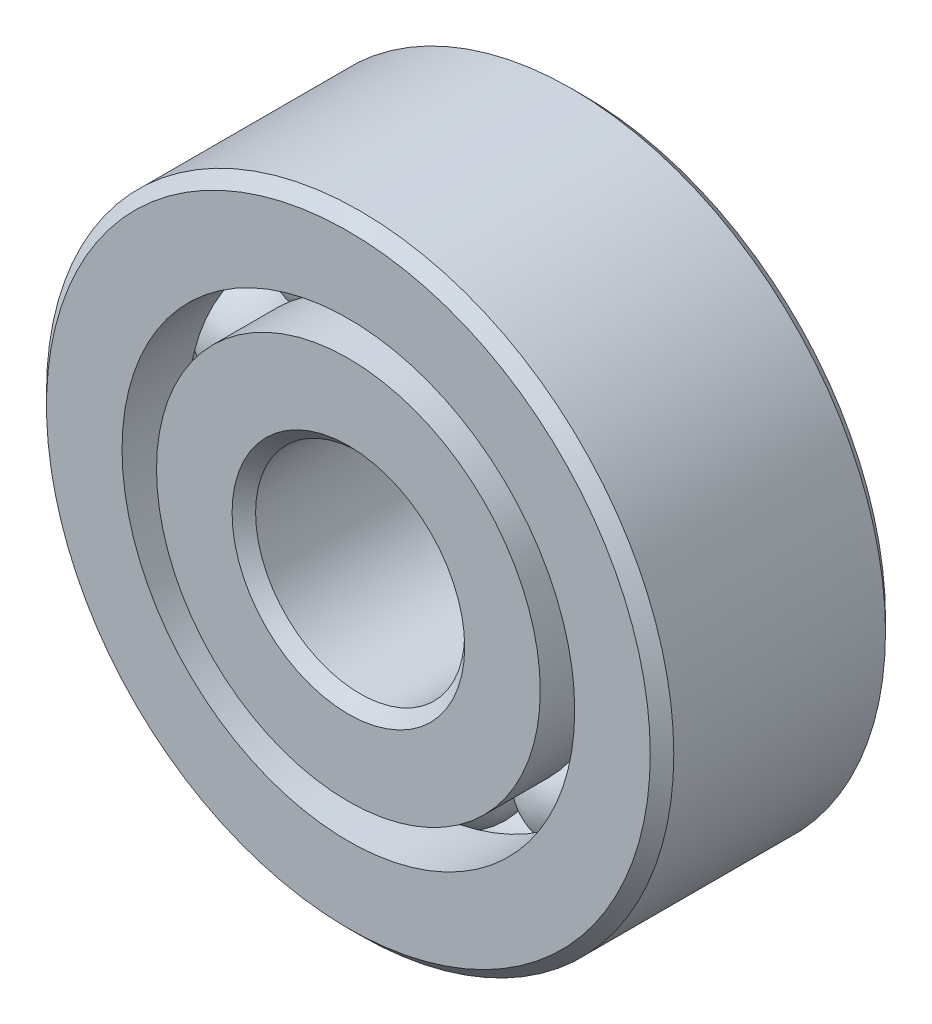
SolidWorks part; units mm, degrees
ref_plane "Front Plane" through (0, 0, 0) normal (0, 0, 1) x (1, 0, 0)
ref_plane "Top Plane" through (0, 0, 0) normal (0, 1, 0) x (1, 0, 0)
ref_plane "Right Plane" through (0, 0, 0) normal (1, 0, 0) x (0, 0, -1)
sketch "Sketch1" plane through (0, 0, 0) normal (1, 0, 0) x (0, 0, -1)
  line L0 (-3.5719, 0) -> (3.5719, 0) construction
  line L1 (0, 9.525) -> (0, -9.525) construction
  line L2 (3.2147, 9.525) -> (-3.2147, 9.525)
  line L3 (-3.2147, 9.525) -> (-3.5719, 9.1678)
  line L4 (-3.5719, 9.1678) -> (-3.5719, 6.8734)
  line L5 (-3.5719, 6.8734) -> (-1.5875, 6.8734)
  line L6 (3.5719, 6.8734) -> (1.5875, 6.8734)
  line L7 (3.5719, 9.1678) -> (3.5719, 6.8734)
  line L8 (3.2147, 9.525) -> (3.5719, 9.1678)
  line L9 (0, 9.525) -> (0, 6.35) construction
  line L10 (0, 6.35) -> (0, 3.175) construction
  arc A0 (-1.5875, 6.8734) -> (1.5875, 6.8734) centre (0, 6.35) cw
  point P14 (0, 3.175)
  dimension "D3" = 3.175
  dimension "D1" = 45
  dimension "Width" = 7.1437
  dimension "OD" = 19.05
  dimension "D2" = 0.3572
  dimension "Shaft Dia" = 6.35
  dimension "D4" = 0.5234
revolve "Revolve1" add sketch "Sketch1" angle 360 about L0
sketch "Sketch3" plane through (0, 0, 0) normal (1, 0, 0) x (0, 0, -1)
  line L0 (-3.5719, 5.8266) -> (-1.5875, 5.8266)
  line L1 (0, 9.525) -> (0, -9.525) construction
  line L2 (-3.5719, 9.1678) -> (-3.5719, 6.8734) construction
  line L3 (-3.5719, 5.8266) -> (-3.5719, 3.5322)
  line L4 (-3.2147, 9.525) -> (-3.5719, 9.1678) construction
  line L5 (-3.5719, 3.5322) -> (-3.2147, 3.175)
  line L6 (-3.2147, 3.175) -> (3.2147, 3.175)
  line L7 (3.2147, 9.525) -> (3.2147, -9.525) construction
  line L8 (3.2147, 3.175) -> (3.5719, 3.5322)
  line L9 (3.5719, -9.1678) -> (3.5719, 9.1678) construction
  line L10 (3.5719, 3.5322) -> (3.5719, 5.8266)
  line L11 (3.5719, 5.8266) -> (1.5875, 5.8266)
  line L13 (3.2147, 9.525) -> (3.5719, 9.1678) construction
  arc A0 (1.5875, 6.8734) -> (-1.5875, 6.8734) centre (0, 6.35) ccw construction
  arc A1 (1.5875, 5.8266) -> (-1.5875, 5.8266) centre (0, 6.35) cw
revolve "Revolve3" add sketch "Sketch3" angle 360 about L0
sketch "Sketch4" plane through (0, 0, 0) normal (1, 0, 0) x (0, 0, -1)
  line L0 (-1.6715, 6.35) -> (1.6715, 6.35)
  arc A2 (-1.6715, 6.35) -> (1.6715, 6.35) centre (0, 6.35) cw
  arc A3 (1.5875, 6.8734) -> (-1.5875, 6.8734) centre (0, 6.35) ccw construction
revolve "Revolve4" add sketch "Sketch4" angle 360 about L0
ref_axis "Axis1" through (0, 0, -3.5719) along (0, 0, 1)
pattern_circular "CirPattern1" count 10 over 360 about axis through (0, 0, -3.5719) along (0, 0, 1) of bodies 104
equation "\"D2@Sketch1\" = \"Width@Sketch1\"*.05"
equation "\"D3@Sketch1\" = \"Width@Sketch1\"/2.25"
equation "\"D4@Sketch1\" = (((\"OD@Sketch1\"-\"Width@Sketch1\")/2)/3.25)/3.5"
equation "\"D2@CirPattern1\" = 360/\"Balls@CirPattern1\""
